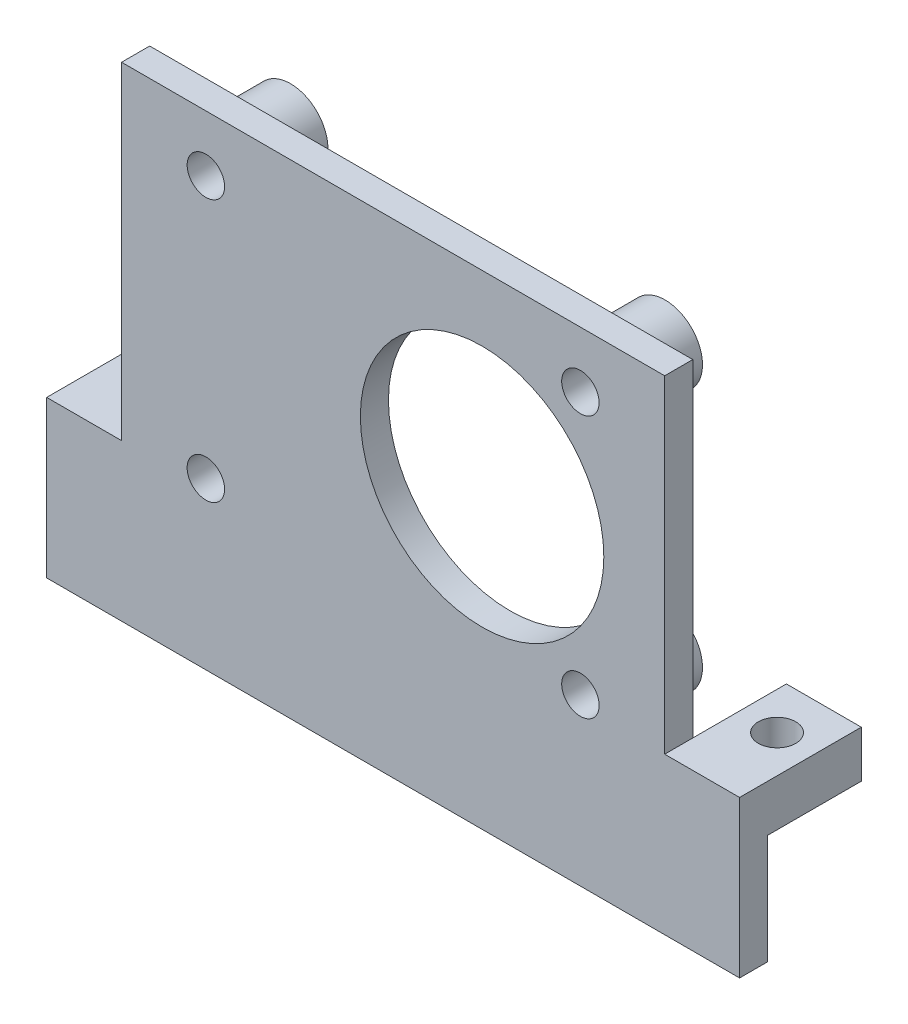
SolidWorks part; units mm, degrees
note: The reader was unsure of these and kept them because the rebuilt part matched: shared geometry of "Sketch1<4>".
ref_plane "Front Plane" through (0, 0, 0) normal (0, 0, 1) x (1, 0, 0)
ref_plane "Top Plane" through (0, 0, 0) normal (0, 1, 0) x (1, 0, 0)
ref_plane "Right Plane" through (0, 0, 0) normal (1, 0, 0) x (0, 0, -1)
sketch "Sketch1" plane through (0, 0, 0) normal (0, 0, 1) x (1, 0, 0)
  line L1 (58, 41.836) -> (58, 1.836) construction
  line L2 (0, 41.836) -> (58, 41.836)
  line L3 (0, 41.836) -> (0, 1.836)
  line L4 (0, 1.836) -> (58, 1.836)
  line L5 (58, 41.836) -> (58, 1.836)
  line L6 (0, 41.836) -> (58, 1.836) construction
  line L7 (0, 1.836) -> (58, 41.836) construction
  line L8 (0, 18.8969) -> (0, 1.836) construction
  line L9 (58, 1.836) -> (0, 1.836) construction
  line L10 (58, 41.836) -> (0, 41.836) construction
  circle A1 centre (9, 35.836) radius 2
  circle A2 centre (9, 7.836) radius 2
  circle A3 centre (49, 35.836) radius 2
  circle A4 centre (38.5, 21.836) radius 13
  circle A5 centre (49, 7.836) radius 2
  circle A7 centre (49, 35.836) radius 4
  circle A8 centre (9, 35.836) radius 4
  circle A9 centre (9, 7.836) radius 4
  circle A10 centre (49, 7.836) radius 4
  point P19 (29, 21.836)
  dimension "D1" = 4
  dimension "D2" = 4
  dimension "D3" = 4
  dimension "D4" = 4
  dimension "D5" = 26
  dimension "D6" = 8
  dimension "D7" = 8
  dimension "D8" = 8
  dimension "D9" = 8
extrude "Boss-Extrude2" add sketch "Sketch1" along normal up to surface (6.0384 mm away) contours A7 A3 | A10 A5 | A9 A2 | A8 A1
sketch "Sketch3" plane through (0, 0, 6.0384) normal (0, 0, 1) x (1, 0, 0)
  line L0 (-45.6524, -9.864) -> (104.3476, -9.864) construction
  line L1 (-8, 1.836) -> (66, 1.836)
  line L2 (-8, 1.836) -> (-8, -9.864)
  line L3 (-8, -9.864) -> (66, -9.864)
  line L4 (66, 1.836) -> (66, -9.864)
  line L5 (-8, 1.836) -> (66, -9.864) construction
  line L6 (-8, -9.864) -> (66, 1.836) construction
  line L8 (-8, 1.836) -> (66, 1.836)
  line L9 (-8, 1.836) -> (-8, 6.836)
  line L10 (-8, 6.836) -> (66, 6.836)
  line L11 (66, 1.836) -> (66, 6.836)
  line L12 (-8, 1.836) -> (66, 6.836) construction
  line L13 (-8, 6.836) -> (66, 1.836) construction
  line L14 (0, 6.836) -> (58, 6.836)
  line L15 (0, 6.836) -> (0, 41.836)
  line L16 (0, 41.836) -> (58, 41.836)
  line L17 (58, 6.836) -> (58, 41.836)
  line L18 (0, 6.836) -> (58, 41.836) construction
  line L19 (0, 41.836) -> (58, 6.836) construction
  point P4 (29, -4.014)
  point P10 (29, 4.336)
  point P16 (29, 24.336)
  dimension "D1" = 74
  dimension "D2" = 35
  dimension "D3" = 58
  dimension "D4" = 5
  dimension "D5" = 11.7
  dimension "D6" = 8
extrude "Boss-Extrude4" add sketch "Sketch3" along normal blind 3
sketch "Sketch2" plane through (0, 1.836, 0) normal (0, 1, 0) x (1, 0, 0)
  line L0 (-45.6524, -6.0384) -> (104.3476, -6.0384) construction
  line L1 (0, 3.9616) -> (-8, 3.9616)
  line L2 (0, 3.9616) -> (0, -6.0384)
  line L3 (0, -6.0384) -> (-8, -6.0384)
  line L4 (-8, 3.9616) -> (-8, -6.0384)
  line L5 (0, 3.9616) -> (-8, -6.0384) construction
  line L6 (0, -6.0384) -> (-8, 3.9616) construction
  line L8 (58, -6.0384) -> (66, -6.0384)
  line L9 (58, -6.0384) -> (58, 3.9616)
  line L10 (58, 3.9616) -> (66, 3.9616)
  line L11 (66, -6.0384) -> (66, 3.9616)
  line L12 (58, -6.0384) -> (66, 3.9616) construction
  line L13 (58, 3.9616) -> (66, -6.0384) construction
  line L14 (0, -9.0384) -> (0, -6.0384) construction
  circle A0 centre (62, -1.0384) radius 2
  circle A1 centre (-4, -1.0384) radius 2
  point P4 (-4, -1.0384)
  point P12 (62, -1.0384)
  dimension "D3" = 4
  dimension "D5" = 4
  dimension "D1" = 8
  dimension "D2" = 10
  dimension "D4" = 8
  dimension "D6" = 58
extrude "Boss-Extrude3" add sketch "Sketch2" along normal blind 5
extrude "Cut-Extrude1" cut sketch "Sketch1<4>" along normal blind 10 contours A1 | A2 | A5 | A3 | A4
sketch "Sketch1<4>" plane through (0, 0, 0) normal (0, 0, 1) x (1, 0, 0) same geometry as "Sketch1"
